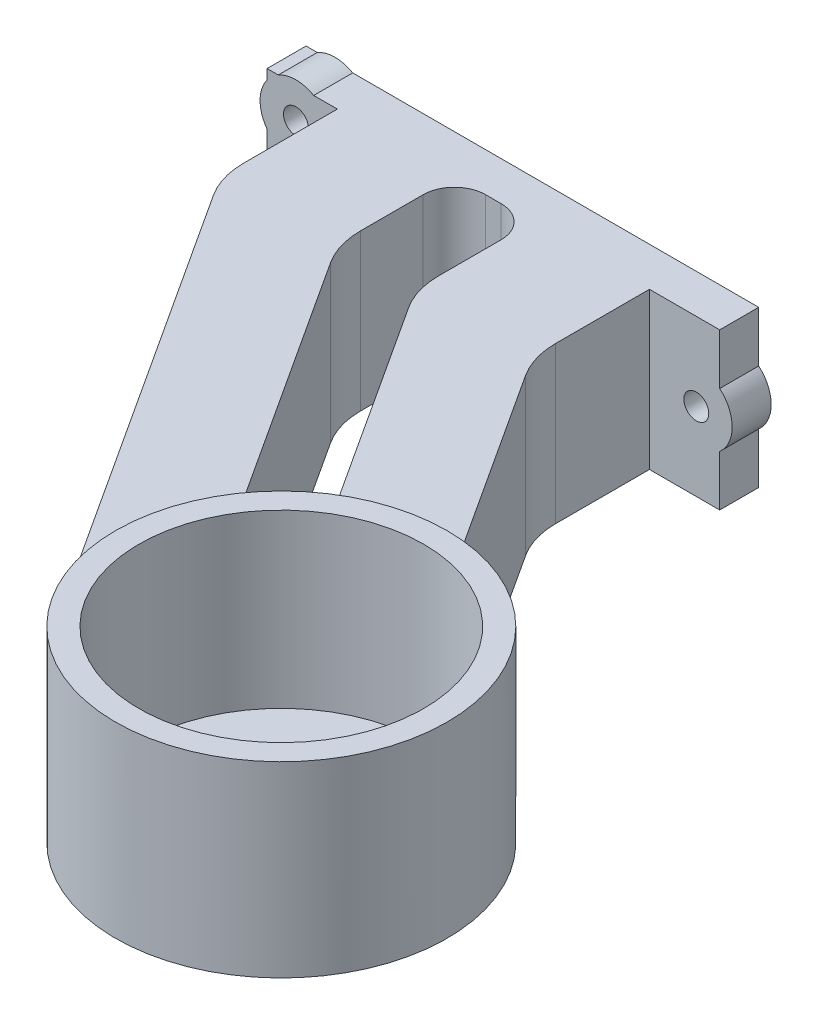
SolidWorks part; units mm, degrees
ref_plane "Front Plane" through (0, 0, 0) normal (0, 0, 1) x (1, 0, 0)
ref_plane "Top Plane" through (0, 0, 0) normal (0, 1, 0) x (1, 0, 0)
ref_plane "Right Plane" through (0, 0, 0) normal (1, 0, 0) x (0, 0, -1)
sketch "Sketch1" plane through (0, 0, 0) normal (0, 1, 0) x (1, 0, 0)
  circle A0 centre (0, 0) radius 18.25
  circle A1 centre (0, 0) radius 21.25
  circle A2 centre (0, 0) radius 11.5
  circle A3 centre (0, 0) radius 14 construction
  circle A4 centre (0, 14) radius 1.6
  circle A5 centre (14, 0) radius 1.6
  circle A6 centre (0, -14) radius 1.6
  circle A7 centre (-14, 0) radius 1.6
  point P18 (0, 0)
  dimension "D1" = 36.5
  dimension "D3" = 23
  dimension "D4" = 28
  dimension "D5" = 3.2
  dimension "D2" = 3
  dimension "D6" = 4
extrude "Boss-Extrude1" add sketch "Sketch1" along normal blind 2 contours A0 A7 A6 A5 A4 A2 region at (-17.7338, 0, 0)
extrude "Boss-Extrude2" add sketch "Sketch1<3>" along normal blind 24 contours A1 A0 region at (-20.649, 0, 0)
sketch "Sketch1<3>" plane through (0, 0, 0) normal (0, 1, 0) x (1, 0, 0) same geometry as "Sketch1"
sketch "Sketch2" plane through (0, 0, 0) normal (0, 1, 0) x (1, 0, 0)
  line L0 (-17.8202, 11.576) -> (-57.8202, -50)
  line L2 (-42.8202, -50) -> (-17.84, -11.5455)
  line L4 (-32.8202, -50) -> (-11.8141, -17.6632)
  line L6 (0.8674, -21.2323) -> (-17.8202, -50)
  line L7 (-57.8202, -50) -> (-57.8202, -70)
  line L8 (-57.8202, -70) -> (-42.8202, -70)
  line L9 (-42.8202, -70) -> (-42.8202, -50)
  line L10 (-32.8202, -50) -> (-32.8202, -70)
  line L11 (-32.8202, -70) -> (-17.8202, -70)
  line L12 (-17.8202, -70) -> (-17.8202, -50)
  circle A0 centre (0, 0) radius 21.25 construction
  circle A1 centre (0, 0) radius 21.25
  dimension "D1" = 15
  dimension "D3" = 40
  dimension "D4" = 10
  dimension "D5" = 20
extrude "Boss-Extrude3" add sketch "Sketch2" along normal blind 20 contours A1 L0 L2 | A1 L4 L6 region at (-39.9825, 0, 36.5409) region at (-19.5746, 0, 45.02)
sketch "Sketch3" plane through (0, 0, 70) normal (0, 0, 1) x (1, 0, 0)
  line L1 (-66.8202, 20) -> (-8.8202, 20)
  line L2 (-66.8202, 20) -> (-66.8202, 0)
  line L3 (-66.8202, 0) -> (-8.8202, 0)
  line L4 (-8.8202, 20) -> (-8.8202, 0)
  line L5 (-63.1184, 16) -> (-63.1184, 4) construction
  line L6 (-42.8202, 0) -> (-32.8202, 0) construction
  line L7 (-57.8202, 20) -> (-42.8202, 20) construction
  circle A0 centre (-37.8202, 10) radius 26 construction
  circle A1 centre (-11.8202, 10) radius 1.6
  circle A2 centre (-63.1184, 16) radius 1.6
  circle A3 centre (-63.1184, 4) radius 1.6
  circle A4 centre (-63.1184, 16) radius 4.6
  circle A5 centre (-63.1184, 4) radius 4.6
  circle A6 centre (-11.8202, 10) radius 4.6
  point P9 (-66.8202, 10)
  point P23 (-37.8202, 0)
  point P24 (-37.8202, 0)
  dimension "D1" = 52
  dimension "D2" = 3.2
  dimension "D3" = 58
  dimension "D4" = 12
  dimension "D5" = 3
extrude "Boss-Extrude4" add sketch "Sketch3" against normal blind 5 contours A6 L4 L1 L3 | L4 A6 A1 | L4 A6 | A5 A4 L2 | A5 A4 | A4 L1 L2 A2 | A5 L2 L3 A3 | A4 | A4 L1 | L1 A4 | A4 L1 L2 | L2 A4 | L2 A5 | A5 L2 L3 | A5 L3 | A5 region at (-66.3783, 19.6068, 70) region at (-63.1184, 20.2414, 70) region at (-63.1184, 19.8805, 70) region at (-67.1826, 16, 70) region at (-36.1624, 10, 70) region at (-61.7184, 8.2561, 70) region at (-67.1826, 4, 70) region at (-8.1695, 10, 70) region at (-8.9395, 10, 70) region at (-66.3783, 0.3932, 70) region at (-63.1184, -0.2414, 70)
fillet "Fillet3" radius 10 4 edges at (-57.8202, 10, 50) (-32.8202, 10, 50) (-42.8202, 10, 50) (-17.8202, 10, 50)
fillet "Fillet4" radius 4 5 edges at (-42.8202, 10, 65) (-32.8202, 10, 65) (-17.84, 10, 11.5455) (0.8674, 10, 21.2323) (-11.8141, 10, 17.6632)
mirror "Mirror1" about plane through (0, 20, 70) normal (0, 0, -1) of bodies 104
delete or keep bodies "Body-Delete/Keep 1" type delete bodies bodies 104
